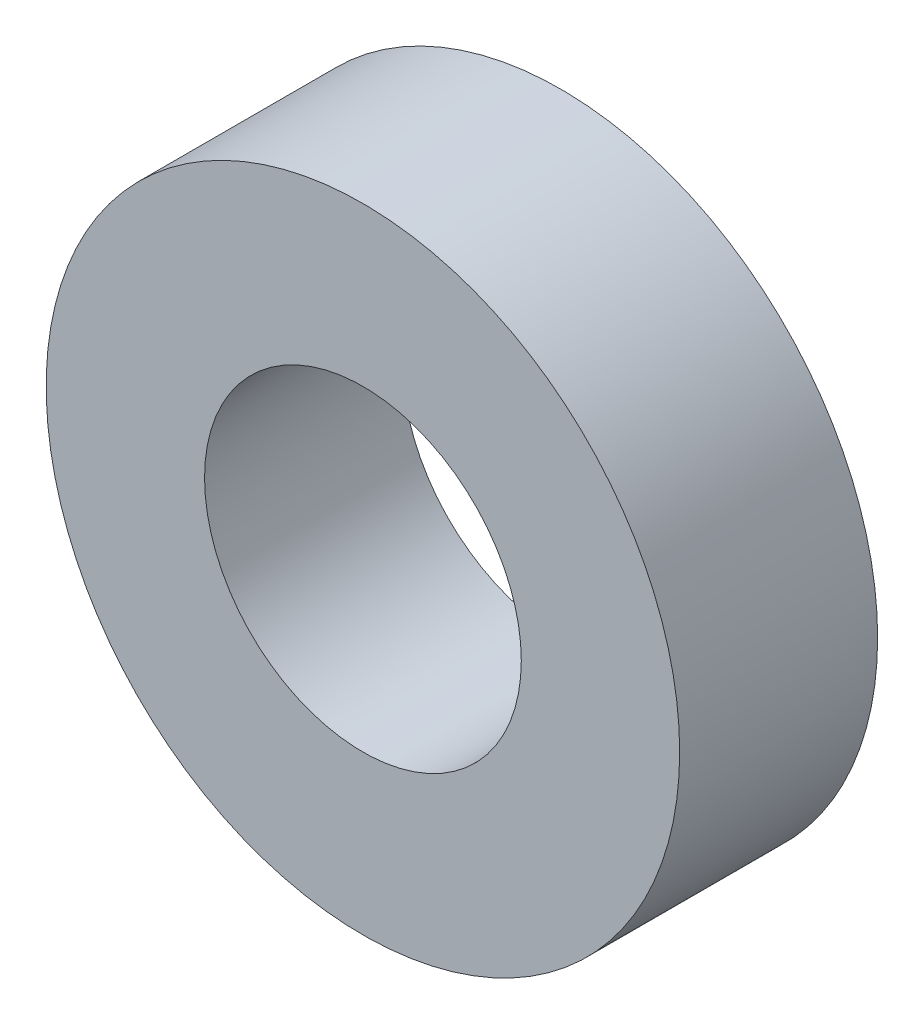
SolidWorks part; units mm, degrees
material "DELRIN"
ref_plane "Front Plane" through (0, 0, 0) normal (0, 0, 1) x (1, 0, 0)
ref_plane "Top Plane" through (0, 0, 0) normal (0, 1, 0) x (1, 0, 0)
ref_plane "Right Plane" through (0, 0, 0) normal (1, 0, 0) x (0, 0, -1)
sketch "Sketch1" plane through (0, 0, 0) normal (0, 0, 1) x (1, 0, 0)
  circle A0 centre (0, 0) radius 2.54
  circle A1 centre (0, 0) radius 5.08
  dimension "D1" = 5.08
  dimension "D2" = 10.16
extrude "Boss-Extrude1" add sketch "Sketch1" along normal blind 3.175
